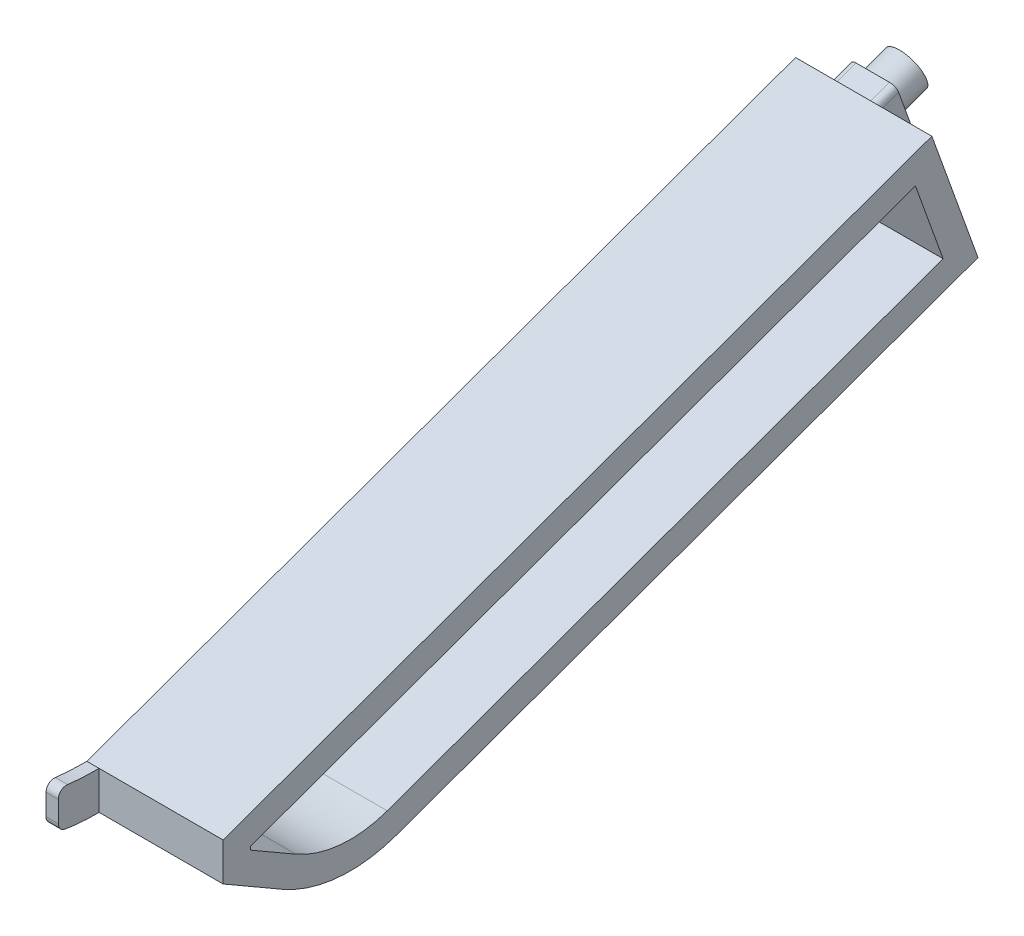
SolidWorks part; units mm, degrees
ref_plane "Front Plane" through (0, 0, 0) normal (0, 0, 1) x (1, 0, 0)
ref_plane "Top Plane" through (0, 0, 0) normal (0, 1, 0) x (1, 0, 0)
ref_plane "Right Plane" through (0, 0, 0) normal (1, 0, 0) x (0, 0, -1)
sketch "Sketch1" plane through (0, 0, 0) normal (1, 0, 0) x (0, 0, -1)
  line L0 (0, 2.8) -> (7.5715, 2.8) construction
  line L1 (-7, 5.1284) -> (-7, -2.9768) construction
  line L2 (0, 0) -> (0, -3.8905) construction
  line L3 (0, 2.8) -> (0, 0) construction
  line L4 (0, 0) -> (-8.3148, 0) construction
  line L5 (-3.7168, 0) -> (3.7562, 0) construction
  line L6 (0, 2.8) -> (-10.0538, 2.8) construction
  line L7 (2.921, 2.8) -> (-2.9257, 2.8) construction
  line L8 (0, 2.8) -> (0, 0)
  spline S0 degree 3 poles (0, 0) (-5.0883, 0) (-6.1015, 1.7391) (-7, 5.1284) knots 0 0 0 0 1 1 1 1
  spline S1 degree 3 poles (-7, 5.1284) (-4.5542, 3.4338) (-3.6542, 2.8) (0, 2.8) knots 0 0 0 0 1 1 1 1
  dimension "D1" = 2.8
  dimension "D2" = 7
extrude "Boss-Extrude1" add sketch "Sketch1" along normal blind 0.9
fillet "Fillet1" radius 0.5 1 edges at (0.45, 5.1284, 7)
sketch "Sketch3" plane through (0, 0, 0) normal (1, 0, 0) x (0, 0, -1)
  line L0 (0, 0) -> (40, 0)
  line L1 (40, 0) -> (40, 10)
  line L2 (40, 10) -> (20, 10)
  line L3 (20, 10) -> (0, 2.8)
  line L4 (0, 2.8) -> (0, 0)
  dimension "D1" = 10
  dimension "D2" = 40
  dimension "D3" = 20
extrude "Boss-Extrude2" add sketch "Sketch3" along normal blind 10
sketch "Sketch5" plane through (0, 0, 0) normal (1, 0, 0) x (0, 0, -1)
  line L0 (0, 0) -> (20, -11.547)
  line L1 (20, -11.547) -> (40, -11.547)
  line L2 (40, -11.547) -> (40, 0)
  line L3 (20, 10) -> (20, -11.547) construction
  line L4 (0, 0) -> (40, 0)
  dimension "D1" = 30
extrude "Boss-Extrude3" add sketch "Sketch5" along normal blind 10 contours L0 L1 L2 L4
sketch "Sketch4" plane through (10, 0, 0) normal (1, 0, 0) x (0, 0, -1)
  line L10 (2, 1.1547) -> (20.5359, -9.547)
  line L11 (38, -9.547) -> (38, 8)
  line L12 (38, 8) -> (20.349, 8)
  line L13 (20.349, 8) -> (2, 1.3943)
  line L15 (38, -9.547) -> (38, 8)
  line L16 (38, 8) -> (20.349, 8)
  line L17 (20.349, 8) -> (2, 1.3943)
  line L19 (2, 1.1547) -> (20.5359, -9.547)
  line L20 (20.5359, -9.547) -> (38, -9.547)
  line L21 (20.5359, -9.547) -> (38, -9.547)
  line L22 (2, 1.3943) -> (2, 1.1547)
  line L23 (2, 1.3943) -> (2, 1.1547)
  dimension "D1" = 2
extrude "Cut-Extrude1" [suppressed] cut sketch "Sketch4" against normal through all
sketch "Sketch6" plane through (10, 0, 0) normal (1, 0, 0) x (0, 0, -1)
  line L0 (8.3515, -4.8217) -> (55.3959, 12.1142)
  line L1 (0, 0) -> (20, -11.547) construction
  line L2 (55.3959, 12.1142) -> (52.0087, 21.5231)
  line L3 (52.0087, 21.5231) -> (20, 10)
  line L4 (20, 10) -> (8.3515, -4.8217)
  line L5 (20, 10) -> (0, 2.8) construction
  dimension "D1" = 10
  dimension "D2" = 50
extrude "Boss-Extrude4" add sketch "Sketch6" against normal up to surface (10 mm away) up to face at (0, 1.1472, -13.3733)
sketch "Sketch7" plane through (10, 0, 0) normal (1, 0, 0) x (0, 0, -1)
  line L0 (40, 6.5717) -> (-6.3967, -10.1311)
  line L1 (-6.3967, -10.1311) -> (25.0314, -20.3196)
  line L2 (25.0314, -20.3196) -> (52.5618, -5.852)
  line L3 (52.5618, -5.852) -> (40, 6.5717)
  line L4 (40, 6.5717) -> (55.3959, 12.1142) construction
extrude "Cut-Extrude2" cut sketch "Sketch7" against normal through all
fillet "Fillet2" radius 10 1 edges at (5, -4.8217, -8.3515)
sketch "Sketch8" plane through (10, 0, 0) normal (1, 0, 0) x (0, 0, -1)
  line L10 (2, 1.1547) -> (5.3316, -0.7688)
  line L11 (12.0414, -1.3677) -> (52.8366, 13.3186)
  line L12 (52.8366, 13.3186) -> (50.8043, 18.9639)
  line L13 (50.8043, 18.9639) -> (2, 1.3943)
  line L14 (2, 1.3943) -> (2, 1.1547)
  line L15 (2, 1.1547) -> (5.3316, -0.7688)
  line L16 (12.0414, -1.3677) -> (52.8366, 13.3186)
  line L17 (52.8366, 13.3186) -> (50.8043, 18.9639)
  line L18 (50.8043, 18.9639) -> (2, 1.3943)
  line L19 (2, 1.3943) -> (2, 1.1547)
  arc A2 (5.3316, -0.7688) -> (12.0414, -1.3677) centre (9.3316, 6.1594) ccw
  arc A3 (5.3316, -0.7688) -> (12.0414, -1.3677) centre (9.3316, 6.1594) ccw
  dimension "D1" = 2
extrude "Cut-Extrude3" cut sketch "Sketch8" against normal through all
sketch "Sketch9" plane through (0, 0, 0) normal (-1, 0, 0) x (0, 0, 1)
  line L0 (0, 0) -> (0, 9.0749) construction
  line L1 (0, 9.0749) -> (3, 9.0749) construction
  line L2 (3, 9.0749) -> (3, -2.6136) construction
  line L3 (3, -0.9887) -> (3, 5.799)
  line L4 (3, 5.799) -> (9.0916, 5.799)
  line L5 (9.0916, 5.799) -> (9.0916, -1.8537)
  line L6 (9.0916, -1.8537) -> (3, -0.9887)
  dimension "D1" = 3
extrude "Cut-Extrude4" cut sketch "Sketch9" against normal through all
fillet "Fillet3" radius 0.6 2 edges at (0.45, 0.2958, 3) (0.45, 3.0492, 3)
sketch "Sketch10" plane through (0, 19.0444, -52.901) normal (0, 0.3387, -0.9409) x (-1, 0, 0)
  line L0 (-5, 2.6345) -> (-5, -7.3655) construction
  line L1 (0, 2.6345) -> (-10, 2.6345) construction
  line L2 (0, -7.3655) -> (-10, -7.3655) construction
  line L3 (-5, -2.3655) -> (0, -2.3655) construction
  line L4 (0, 2.6345) -> (0, -7.3655) construction
  circle A0 centre (-5, -2.3655) radius 2.1
  dimension "D1" = 4.2
extrude "Boss-Extrude5" add sketch "Sketch10" along normal blind 3
sketch "Sketch11" plane through (0, 20.0605, -55.7237) normal (0, 0.3387, -0.9409) x (-1, 0, 0)
  circle A0 centre (-5, -2.3655) radius 1.5
  dimension "D1" = 3
extrude "Boss-Extrude6" add sketch "Sketch11" along normal blind 2
sketch "Sketch12" plane through (10, 0, 0) normal (1, 0, 0) x (0, 0, -1)
  line L0 (0, 2.8) -> (1.7953, -2.1324)
  line L1 (1.7953, -2.1324) -> (-2.7062, -1.6531)
  line L2 (-2.7062, -1.6531) -> (0, 2.8)
  line L3 (0, 2.8) -> (0, 0) construction
  dimension "D1" = 20
extrude "Cut-Extrude5" [suppressed] cut sketch "Sketch12" against normal up to surface (9.1 mm away) up to face at (0.9, 1.289, 1.8603)
split "Split1" bodies to split 110 resulting bodies 112 113 split by face at (5, 18.7945, -52.9909)
sketch "Sketch13" plane through (0, 19.0444, -52.901) normal (0, 0.3387, -0.9409) x (-1, 0, 0)
  line L0 (-10, -2.3655) -> (2.9298, -2.3655) construction
  line L1 (-10, -7.3655) -> (-10, 2.6345) construction
  line L2 (0, 2.6345) -> (0, -7.3655) construction
  line L3 (-3.4648, -4.0979) -> (0, -4.0979)
  line L4 (-3.4648, -4.0979) -> (-3.4648, -0.6331)
  line L5 (-3.4648, -0.6331) -> (0, -0.6331)
  line L6 (0, -4.0979) -> (0, -0.6331)
  line L7 (-3.4648, -4.0979) -> (0, -0.6331) construction
  line L8 (-3.4648, -0.6331) -> (0, -4.0979) construction
  circle A0 centre (-1.7324, -2.3655) radius 2.45 construction
  point P4 (-1.7324, -2.3655)
  dimension "D1" = 4.9
  dimension "D2" = 3.4648
extrude "Boss-Extrude7" add sketch "Sketch13" along normal up to surface (3 mm away) separate body up to face at (5, 19.2462, -56.0168)
sketch "Sketch14" plane through (0, 20.0605, -55.7237) normal (0, 0.3387, -0.9409) x (-1, 0, 0)
  line L0 (0, -2.3655) -> (-3.4648, -2.3655) construction
  line L1 (0, -4.0979) -> (0, -0.6331) construction
  line L2 (-3.4648, -0.6331) -> (-3.4648, -4.0979) construction
  circle A0 centre (-1.7324, -2.3655) radius 1.5
  dimension "D1" = 3
extrude "Boss-Extrude8" add sketch "Sketch14" along normal up to surface (2 mm away) separate body up to face at (5, 19.9236, -57.8986)
delete or keep bodies "Body-Delete/Keep 1" type delete bodies bodies 112
combine bodies "Combine1" operation type add bodies to combine 113 114 115
fillet "Fillet4" radius 0.5 4 edges at (3.4648, 15.6968, -55.7004) (0, 15.6968, -55.7004) (3.4648, 18.9568, -54.5268) (0, 18.9568, -54.5268)
sketch "Sketch16" plane through (10, 0, 0) normal (1, 0, 0) x (0, 0, -1)
  line L0 (12.7188, -3.2495) -> (14.8631, -9.2059)
  line L1 (4.3316, -2.5009) -> (7.1194, -10.2447)
  line L2 (0, 0) -> (3.1658, -8.794)
  line L3 (12.7188, -3.2495) -> (55.3959, 12.1142) construction
  line L4 (12.7188, -3.2495) -> (55.3959, 12.1142) construction
  line L5 (0, 0) -> (4.3316, -2.5009) construction
  line L6 (0, 0) -> (4.3316, -2.5009)
  line L7 (0, 2.8) -> (0, 0) construction
  line L8 (0, 2.8) -> (0, 0)
  line L9 (-3, 0.7819) -> (-3, 2.3348) construction
  line L10 (-3, 0.7819) -> (-3, 2.3348)
  arc A0 (-3, 0.7819) -> (-2.5068, 0.1915) centre (-2.4, 0.7819) ccw construction
  arc A1 (-2.3182, 2.9292) -> (-3, 2.3348) centre (-2.4, 2.3348) ccw construction
  arc A2 (-3, 0.7819) -> (-2.5068, 0.1915) centre (-2.4, 0.7819) ccw
  arc A3 (-2.3182, 2.9292) -> (-3, 2.3348) centre (-2.4, 2.3348) ccw
  spline S0 degree 3 poles (-1967.1238, 351.3101) (1933.8337, -26.789) (-1956.9875, -168.5872) (1980.3579, 276.7089) knots -7.910374 -7.910374 -7.910374 -7.910374 7.889269 7.889269 7.889269 7.889269 only from (-2.5068, 0.1915) to (0, 0) construction
  spline S1 degree 3 poles (1998.9952, -52.5648) (-1936.261, 136.3687) (1913.179, -234.4821) (-1966.5988, 375.8099) knots -7.055546 -7.055546 -7.055546 -7.055546 8.281716 8.281716 8.281716 8.281716 only from (0, 2.8) to (-2.3182, 2.9292) construction
  spline S2 degree 3 poles (-2.5068, 0.1915) (-1.8026, 0.064) (-0.9763, 0) (0, 0) knots 0.808125 0.808125 0.808125 0.808125 1 1 1 1
  spline S3 degree 3 poles (0, 2.8) (-0.9264, 2.8) (-1.6758, 2.8407) (-2.3182, 2.9292) knots 0 0 0 0 0.253512 0.253512 0.253512 0.253512
  dimension "D1" = 7.6378
  dimension "D2" = 3.2285
  dimension "D3" = 49.799
  dimension "D4" = 120
